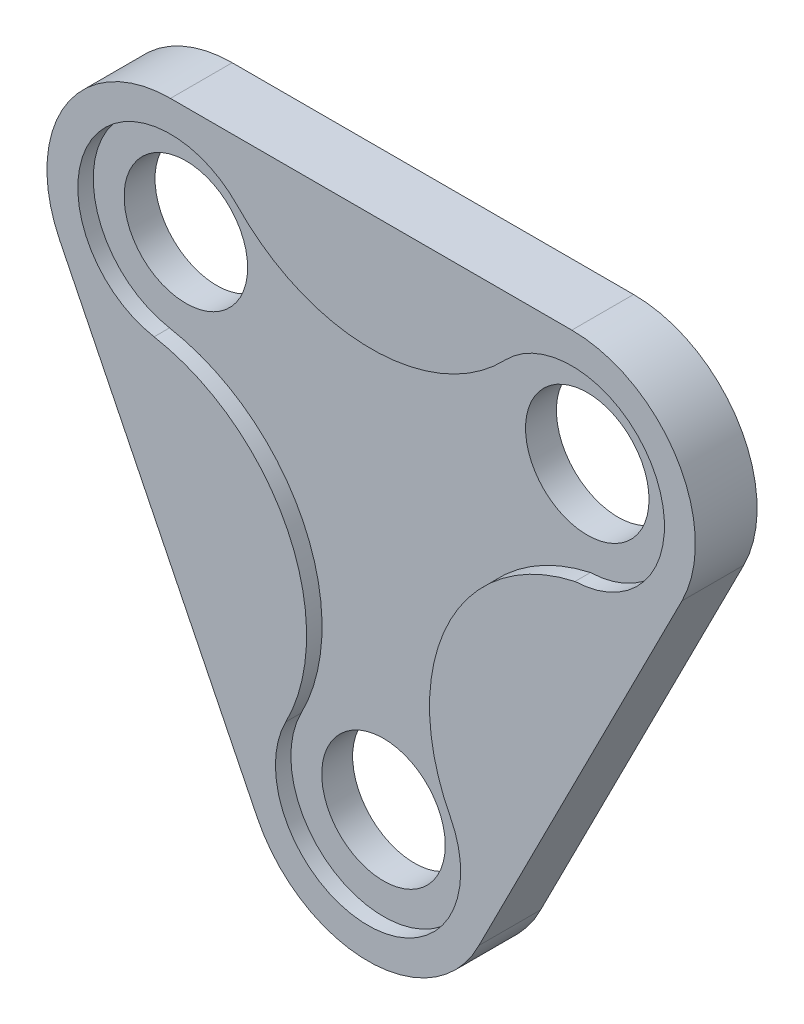
SolidWorks part; units mm, degrees
ref_plane "Front Plane" through (0, 0, 0) normal (0, 0, 1) x (1, 0, 0)
ref_plane "Top Plane" through (0, 0, 0) normal (0, 1, 0) x (1, 0, 0)
ref_plane "Right Plane" through (0, 0, 0) normal (1, 0, 0) x (0, 0, -1)
sketch "Sketch1" plane through (0, 0, 0) normal (0, 0, 1) x (1, 0, 0)
  line L0 (0, 0) -> (0, 40.7815) construction
  line L1 (-32, 85) -> (33, 85)
  line L2 (-17.9434, -8.8337) -> (-49.9434, 56.1663)
  line L3 (17.9434, -8.8337) -> (50.8331, 55.9458)
  circle A0 centre (-32, 65) radius 10
  circle A1 centre (33, 65) radius 10
  circle A2 centre (0, 0) radius 10
  arc A3 (-13.3174, 6.9027) -> (13.3174, 6.9027) centre (0, 0) ccw
  arc A4 (-21.1667, 75.3749) -> (-34.6507, 50.2361) centre (-32, 65) ccw
  arc A5 (33.5117, 50.0087) -> (22.1667, 75.3749) centre (33, 65) ccw
  arc A6 (-21.1667, 75.3749) -> (22.1667, 75.3749) centre (0.5, 96.1247) ccw
  arc A7 (-34.6507, 50.2361) -> (-13.3174, 6.9027) centre (-39.9521, 20.7082) cw
  arc A8 (34.6507, 50.2361) -> (13.3174, 6.9027) centre (39.9521, 20.7082) ccw
  arc A9 (-32, 85) -> (-49.9434, 56.1663) centre (-32, 65) ccw
  arc A10 (50.8331, 55.9458) -> (33, 85) centre (33, 65) ccw
  arc A11 (-17.9434, -8.8337) -> (17.9434, -8.8337) centre (0, 0) ccw
  point P27 (0, 0)
  point P30 (52.4389, 46.0727)
  point P31 (0, 0)
  dimension "D1" = 20
  dimension "D2" = 20
  dimension "D3" = 65
  dimension "D4" = 33
  dimension "D5" = 65
  dimension "D6" = 30
  dimension "D7" = 30
  dimension "D8" = 40
extrude "Boss-Extrude1" add sketch "Sketch1" along normal mid plane 10 contours L2 A11 L3 A10 L1 A9 A5 A8 A3 A7 A4 A6 region at (0.5, 83.5151, 0)
extrude "Boss-Extrude2" add sketch "Sketch1<3>" along normal mid plane 5 contours A8 A5 A6 A4 A7 A3 A2 A1 A0 region at (0.2529, 44.1543, 0)
sketch "Sketch1<3>" plane through (0, 0, 0) normal (0, 0, 1) x (1, 0, 0) same geometry as "Sketch1"
